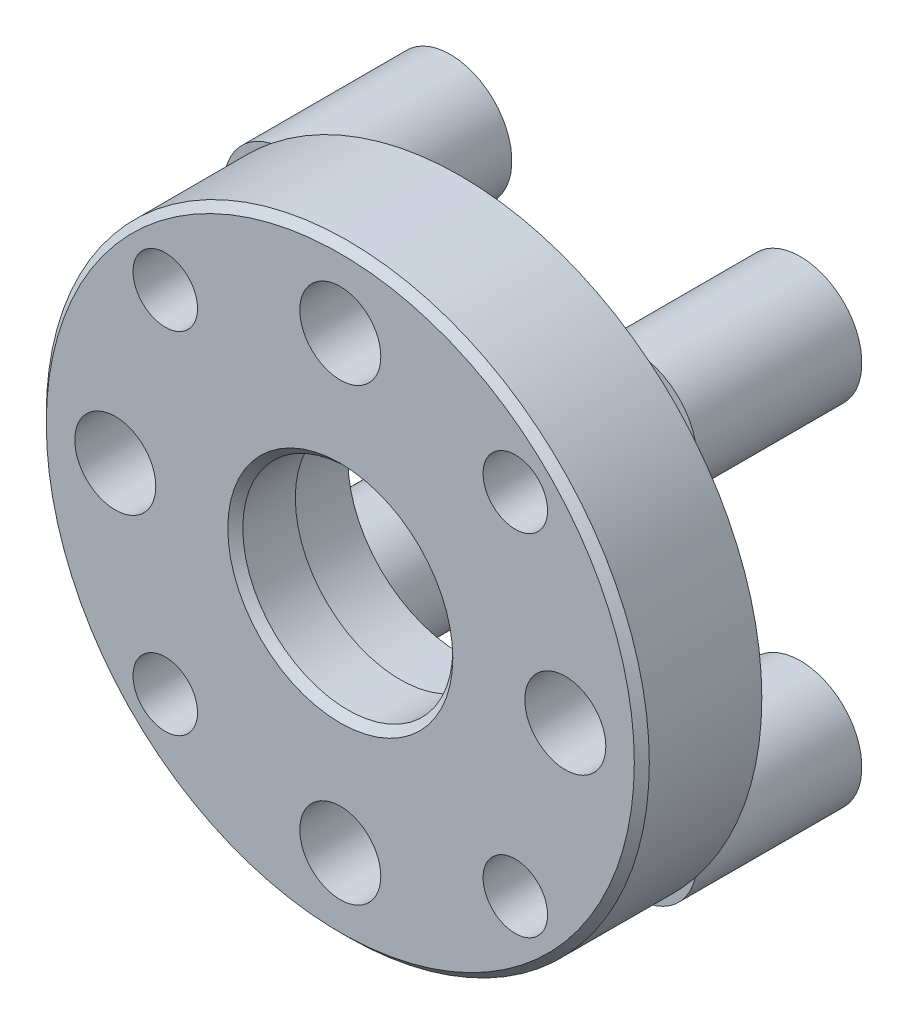
SolidWorks part; units mm, degrees
material "ABS"
ref_plane "Front Plane" through (0, 0, 0) normal (0, 0, 1) x (1, 0, 0)
ref_plane "Top Plane" through (0, 0, 0) normal (0, 1, 0) x (1, 0, 0)
ref_plane "Right Plane" through (0, 0, 0) normal (1, 0, 0) x (0, 0, -1)
ref_plane "Output Plane" through (0, 0, 25.2347) normal (0, 0, -1) x (-1, 0, 0)
sketch "CYC Output Sketch" plane through (0, 0, 25.2347) normal (0, 0, 1) x (1, 0, 0)
  line L1 (11.6673, 11.6673) -> (-11.6673, 11.6673) construction
  line L2 (-11.6673, 11.6673) -> (-11.6673, -11.6673) construction
  line L3 (-11.6673, -11.6673) -> (11.6673, -11.6673) construction
  line L4 (11.6673, -11.6673) -> (11.6673, 11.6673) construction
  circle A0 centre (0, 0) radius 16.5 construction
sketch "Sketch3" plane through (0, 0, 25.2347) normal (0, 0, -1) x (-1, 0, 0)
  circle A0 centre (-11.6673, 11.6673) radius 4
  circle A1 centre (11.6673, 11.6673) radius 4
  circle A2 centre (11.6673, -11.6673) radius 4
  circle A3 centre (-11.6673, -11.6673) radius 4
  dimension "D1" = 8
extrude "Boss-Extrude1" add sketch "Sketch3" along normal blind 11
sketch "Sketch6" plane through (0, 0, 25.2347) normal (0, 0, 1) x (1, 0, 0)
  arc A0 (10.7357, 16.9928) -> (-16.9928, 10.7357) centre (0, 0) ccw
  arc A18 (16.9928, -10.7357) -> (10.7357, 16.9928) centre (0, 0) ccw
  arc A19 (-10.7357, -16.9928) -> (16.9928, -10.7357) centre (0, 0) ccw
  arc A20 (-16.9928, 10.7357) -> (-10.7357, -16.9928) centre (0, 0) ccw
  circle A23 centre (0, 0) radius 7.5
  dimension "D2" = 40.2
  dimension "D1" = 15
extrude "Boss-Extrude6" add sketch "Sketch6" along normal blind 8 contours A23 | A0 A20 A19 A18 region at (0, 0, 25.2347)
sketch "Sketch8" plane through (0, 0, 33.2347) normal (0, 0, 1) x (1, 0, 0)
  line L0 (0, 0) -> (11.6673, 11.6673) construction
  line L1 (0, 0) -> (16.5, 0) construction
  circle A0 centre (0, 0) radius 16.5 construction
  circle A1 centre (11.6673, 11.6673) radius 1.6
  circle A2 centre (11.6673, -11.6673) radius 1.6
  circle A3 centre (-11.6673, -11.6673) radius 1.6
  circle A4 centre (-11.6673, 11.6673) radius 1.6
  point P16 (0, 0)
  dimension "D1" = 33
  dimension "D2" = 45
  dimension "D3" = 3.2
  dimension "D4" = 4
extrude "Cut-Extrude1" cut sketch "Sketch8" against normal through all
sketch "Sketch9" plane through (0, 0, 14.2347) normal (0, 0, 1) x (1, 0, 0)
  circle A0 centre (11.6673, 11.6673) radius 3
  circle A1 centre (11.6673, -11.6673) radius 3
  circle A2 centre (-11.6673, -11.6673) radius 3
  circle A3 centre (-11.6673, 11.6673) radius 3
  point P12 (0, 0)
  dimension "D1" = 6
  dimension "D2" = 4
extrude "Cut-Extrude2" cut sketch "Sketch9" along normal blind 3 from surface starting at face at (13.2673, 11.6673, 14.2347)
sketch "Sketch10" plane through (0, 0, 14.2347) normal (0, 0, -1) x (-1, 0, 0)
  circle A0 centre (11.6673, 11.6673) radius 4.1
  circle A1 centre (11.6673, 11.6673) radius 4
  circle A2 centre (11.6673, -11.6673) radius 4
  circle A3 centre (11.6673, -11.6673) radius 4.1
  circle A4 centre (-11.6673, -11.6673) radius 4
  circle A5 centre (-11.6673, -11.6673) radius 4.1
  circle A6 centre (-11.6673, 11.6673) radius 4
  circle A7 centre (-11.6673, 11.6673) radius 4.1
  point P16 (0, 0)
  dimension "D1" = 8
  dimension "D2" = 8.2
  dimension "D3" = 4
extrude "Boss-Extrude8" add sketch "Sketch10" against normal blind 11
sketch "Sketch11" plane through (0, 0, 33.2347) normal (0, 0, 1) x (1, 0, 0)
  line L0 (0, 0) -> (0, 15) construction
  circle A0 centre (0, 15) radius 2.7
  circle A1 centre (15, 0) radius 2.7
  circle A2 centre (0, -15) radius 2.7
  circle A3 centre (-15, 0) radius 2.7
  circle A4 centre (-11.6673, 11.6673) radius 2.15
  circle A5 centre (11.6673, 11.6673) radius 2.15
  circle A6 centre (11.6673, -11.6673) radius 2.15
  circle A7 centre (-11.6673, -11.6673) radius 2.15
  point P13 (0, 0)
  dimension "D2" = 5.4
  dimension "D4" = 4.3
  dimension "D1" = 15
  dimension "D3" = 4
extrude "Cut-Extrude3" cut sketch "Sketch11" against normal blind 8
sketch "Sketch12" plane through (0, 0, 33.2347) normal (0, 0, 1) x (1, 0, 0)
  circle A0 centre (0, 0) radius 7.5
  circle A1 centre (0, 0) radius 7
  dimension "D1" = 15
  dimension "D2" = 14
extrude "Boss-Extrude9" add sketch "Sketch12" against normal blind 4
chamfer "Chamfer1" distance 0.5 angle 45 2 edges at (7, 0, 33.2347) (20.1, 0, 33.2347)
equation "\"RingPinShaft\"= 5.05"
equation "\"CenterBearingOut\"=32.00"
equation "\"RingPostIn\"=5.15"
equation "\"CamBearingOut\"=15.1"
equation "\"DiskOutputShaft\"=10.1"
equation "\"CenterShaft\"=25.2"
equation "\"Eccentricity\"=2"
equation "\"CycCamShaft\"=10.05"
equation "\"D2@Sketch6\"=\"OutputBearing\""
equation "\"OutputBearing\"=40.2"
